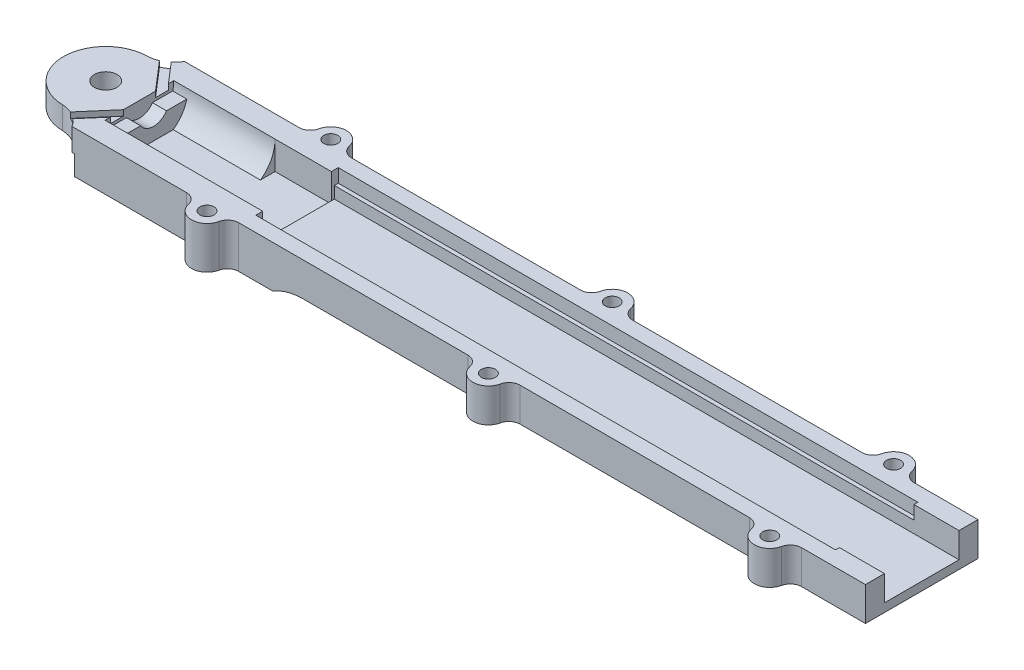
SolidWorks part; units mm, degrees
ref_plane "Front Plane" through (0, 0, 0) normal (0, 0, 1) x (1, 0, 0)
ref_plane "Top Plane" through (0, 0, 0) normal (0, 1, 0) x (1, 0, 0)
ref_plane "Right Plane" through (0, 0, 0) normal (1, 0, 0) x (0, 0, -1)
sketch "Sketch1" plane through (0, 0, 0) normal (0, 1, 0) x (1, 0, 0)
  line L0 (-32.4167, 0) -> (142.483, 0) construction
  line L3 (0, 10) -> (141, 10)
  line L4 (141, 10) -> (141, -10)
  line L5 (141, -10) -> (0, -10)
  line L8 (0, 10) -> (0, -10)
  line L9 (-4, 7.5) -> (0, 7.5)
  line L10 (-4, -7.5) -> (0, -7.5)
  circle A0 centre (-4, 0) radius 2
  arc A1 (-4, 7.5) -> (-4, -7.5) centre (-4, 0) ccw
  point P15 (141, 0)
  dimension "D1" = 4
  dimension "D2" = 4
  dimension "D3" = 145
  dimension "D5" = 7.5
  dimension "D4" = 20
extrude "Boss-Extrude1" add sketch "Sketch1" along normal mid plane 8 contours A1 L0 A0 L8 L3 | L0 A1 L5 L8 A0 region at (-5.1875, 0, -3.6496) region at (-5.1875, 0, 3.6496)
extrude "Boss-Extrude2" add sketch "Sketch1<3>" along normal mid plane 12 contours L8 L0 L4 L3 | L0 L8 L5 L4 region at (70.5, 0, -5) region at (70.5, 0, 5)
sketch "Sketch1<3>" plane through (0, 0, 0) normal (0, 1, 0) x (1, 0, 0) same geometry as "Sketch1"
sketch "Sketch3" plane through (0, 0, 0) normal (-1, 0, 0) x (0, 0, 1)
  line L0 (-3.4943, -5) -> (3.4943, -5)
  line L1 (-6.1, 0) -> (-6.1, 6)
  line L2 (-10, 6) -> (10, 6) construction
  line L3 (-6.1, 6) -> (6.1, 6)
  line L4 (6.1, 6) -> (6.1, 0)
  arc A0 (3.4943, -5) -> (6.1, 0) centre (0, 0) ccw
  arc A1 (-6.1, 0) -> (-3.4943, -5) centre (0, 0) ccw
  dimension "D1" = 12.2
  dimension "D2" = 5
extrude "Cut-Extrude1" cut sketch "Sketch3" against normal blind 18 from offset 2 offset against normal yes
sketch "Sketch4" plane through (20, 0, 0) normal (-1, 0, 0) x (0, 0, 1)
  line L0 (-6.1, 6) -> (-6.1, -5)
  line L1 (-6.1, -5) -> (6.1, -5)
  line L2 (6.1, -5) -> (6.1, 6)
  line L3 (6.1, 6) -> (-6.1, 6)
  dimension "D1" = 11
extrude "Cut-Extrude2" cut sketch "Sketch4" against normal blind 10
sketch "Sketch5" plane through (0, 0, 0) normal (-1, 0, 0) x (0, 0, 1)
  line L1 (-10, -6) -> (10, -6)
  line L2 (-10, -6) -> (-10, -8)
  line L3 (-10, -8) -> (10, -8)
  line L4 (10, -6) -> (10, -8)
  dimension "D1" = 20
  dimension "D2" = 2
extrude "Boss-Extrude3" add sketch "Sketch5" against normal blind 35
sketch "Sketch13" plane through (30, 0, 0) normal (-1, 0, 0) x (0, 0, 1)
  line L4 (-6.625, 5) -> (-6.625, -1)
  line L9 (-6.625, -1) -> (-6.625, -5)
  line L12 (-6.625, -5) -> (6.625, -5)
  line L15 (6.625, -5) -> (6.625, -1)
  line L19 (6.625, -1) -> (6.625, 5)
  line L20 (6.625, 5) -> (-6.625, 5)
  line L21 (0, 8.1097) -> (0, -11.293) construction
  point P23 (0, -5)
  point P24 (0, 5)
  dimension "D1" = 5
  dimension "D2" = 5
  dimension "D5" = 13.25
extrude "Cut-Extrude7" cut sketch "Sketch13" against normal through all
sketch "Sketch14" plane through (0, 0, 0) normal (-1, 0, 0) x (0, 0, 1)
  line L0 (10, 6) -> (10, -8) construction
  line L1 (-10, 6) -> (10, 6)
  line L2 (-10, 6) -> (-10, 4)
  line L3 (-10, 4) -> (10, 4)
  line L4 (10, 6) -> (10, 4)
  dimension "D1" = 2
extrude "Cut-Extrude8" cut sketch "Sketch14" against normal through all
fillet "Fillet2" radius 10 1 edges at (35, -6, 0)
fillet "Fillet3" radius 5 2 edges at (0, 0, 7.5) (0, 0, -7.5)
sketch "Sketch16" plane through (2, 0, 0) normal (1, 0, 0) x (0, 0, -1)
  line L0 (-6.1, 1.5) -> (-2.3049, 1.5)
  line L1 (2.3049, 1.5) -> (6.1, 1.5)
  line L2 (-5.9127, -1.5) -> (-2.3049, -1.5)
  line L3 (2.3049, -1.5) -> (5.9127, -1.5)
  line L4 (6.1, 0) -> (6.1, 4)
  line L5 (6.1, 0) -> (6.1, 4)
  line L7 (-3.4943, -5) -> (3.4943, -5)
  line L11 (-3.4943, -5) -> (3.4943, -5)
  line L16 (6.1, 4) -> (-6.1, 4)
  line L17 (6.1, 4) -> (-6.1, 4)
  line L18 (-6.1, 4) -> (-6.1, 0)
  line L19 (-6.1, 4) -> (-6.1, 0)
  arc A0 (-2.3049, -1.5) -> (2.3049, -1.5) centre (0, 0) ccw
  arc A1 (2.3049, 1.5) -> (-2.3049, 1.5) centre (0, 0) ccw
  arc A3 (-6.1, 0) -> (-3.4943, -5) centre (0, 0) ccw
  arc A4 (3.4943, -5) -> (6.1, 0) centre (0, 0) ccw
  arc A5 (-5.9127, -1.5) -> (-3.4943, -5) centre (0, 0) ccw
  arc A6 (3.4943, -5) -> (5.9127, -1.5) centre (0, 0) ccw
  arc M13 (-6.1, 0) -> (-3.4943, -5) centre (0, 0) ccw
  line M14 (-3.4943, -5) -> (3.4943, -5)
  arc M15 (3.4943, -5) -> (6.1, 0) centre (0, 0) ccw
  dimension "D1" = 0
  dimension "D2" = 5.5
  dimension "D3" = 1.5
  dimension "D4" = 1.5
sketch "Sketch20" plane through (0, 0, 0) normal (1, 0, 0) x (0, 0, -1)
  line L0 (10, 4) -> (10, -4) construction
  line L1 (10, 0) -> (-10, 0)
  line L2 (10, 0) -> (10, 4)
  line L3 (10, 4) -> (-10, 4)
  line L4 (-10, 0) -> (-10, 4)
extrude "Cut-Extrude10" cut sketch "Sketch20" against normal through all and the other way through all
extrude "Boss-Extrude5" add sketch "Sketch16" along normal blind 2.5 contours A0 L2 L3 M13 M14 M15 region at (2, -3.2591, 0)
sketch "Sketch22" plane through (0, 0, 0) normal (0, 1, 0) x (1, 0, 0)
  line L0 (-4, 0) -> (14.7321, 0) construction
  line L1 (-3.6253, 4) -> (18.01, 4) construction
  line L2 (2, 5.15) -> (2, 2.85)
  line L3 (2, 2.3049) -> (2, 5.9127) construction
  line L4 (2, 6.1) -> (2, -6.1) construction
  line L5 (2, 2.85) -> (-2.3495, 7.9057)
  line L6 (-2.3495, 7.9057) -> (-1.0642, 8.7118)
  line L7 (-1.0642, 8.7118) -> (2, 5.15)
  line L8 (2, -5.15) -> (2, -2.85)
  line L9 (-1.0642, -8.7118) -> (2, -5.15)
  line L10 (2, -2.85) -> (-2.3495, -7.9057)
  line L11 (-2.3495, -7.9057) -> (-1.0642, -8.7118)
  arc A1 (-4.1996, 7.4973) -> (0, 10) centre (-4.3327, 12.4956) ccw construction
  point P16 (2, 4)
  dimension "D2" = 1.5
  dimension "D1" = 4
  dimension "D3" = 2.3
extrude "Cut-Extrude11" cut sketch "Sketch22" against normal blind 1
sketch "Sketch25" plane through (141, 0, 0) normal (1, 0, 0) x (0, 0, -1)
  line L0 (-10, 0) -> (-10, -6) construction
  line L1 (-10, -6) -> (-10, -8)
  line L2 (-10, -8) -> (10, -8)
  line L3 (-10, -6) -> (10, -6)
  line L4 (10, -6) -> (10, -8)
  dimension "D1" = 6
  dimension "D2" = 2
  dimension "D3" = 20
sketch "Sketch26" plane through (141, 0, 0) normal (1, 0, 0) x (0, 0, -1)
  line L0 (6.625, 0) -> (6.625, -5) construction
  line L1 (-6.625, -5) -> (6.625, -5)
  line L2 (-6.625, -5) -> (-6.625, -4.5)
  line L3 (-6.625, -4.5) -> (6.625, -4.5)
  line L4 (6.625, -5) -> (6.625, -4.5)
  dimension "D1" = 0.5
extrude "Boss-Extrude6" add sketch "Sketch26" against normal up to surface (111 mm away) up to face at (30, -2.5, 6.3625)
sketch "Sketch31" plane through (0, 0, 0) normal (0, 1, 0) x (1, 0, 0)
  line L3 (-4.4, 0) -> (4.4, 0) construction
  circle A1 centre (25, 11) radius 2.75
  circle A2 centre (25, 11) radius 1.25
  circle A3 centre (75, 11) radius 2.75
  circle A4 centre (75, 11) radius 1.25
  circle A5 centre (125, 11) radius 2.75
  circle A6 centre (125, 11) radius 1.25
  circle A7 centre (125, -11) radius 1.25
  circle A8 centre (125, -11) radius 2.75
  circle A9 centre (75, -11) radius 1.25
  circle A10 centre (75, -11) radius 2.75
  circle A11 centre (25, -11) radius 1.25
  circle A12 centre (25, -11) radius 2.75
  dimension "D1" = 2.5
  dimension "D2" = 5.5
  dimension "D4" = 11
  dimension "D3" = 25
  dimension "D6" = 50
  dimension "D5" = 3
extrude "Boss-Extrude8" add sketch "Sketch31" against normal through all contours A12 | A11 | A1 | A2
extrude "Boss-Extrude9" add sketch "Sketch31<5>" against normal up to surface (6 mm away) up to face at (91, -6, 0)
sketch "Sketch31<5>" plane through (0, 0, 0) normal (0, 1, 0) x (1, 0, 0) same geometry as "Sketch31"
sketch "Sketch33" plane through (0, 0, 0) normal (0, 1, 0) x (1, 0, 0)
  circle A0 centre (25, 11) radius 1.25
  circle A1 centre (75, 11) radius 1.25
  circle A2 centre (75, -11) radius 1.25
  circle A3 centre (25, -11) radius 1.25
  circle A4 centre (125, 11) radius 1.25
  circle A5 centre (125, -11) radius 1.25
  arc A6 (24.25, -10) -> (25.75, -10) centre (25, -11) ccw construction
extrude "Cut-Extrude12" cut sketch "Sketch33" against normal through all
fillet "Fillet4" radius 2 12 edges at (122.4383, -3, -10) (72.4383, -3, -10) (22.4383, -4, -10) (127.5617, -3, -10) (77.5617, -3, -10) (27.5617, -4, -10) (127.5617, -3, 10) (77.5617, -3, 10) (122.4383, -3, 10) (72.4383, -3, 10) (22.4383, -4, 10) (27.5617, -4, 10)
sketch "Sketch34" plane through (0, 0, 0) normal (0, 1, 0) x (1, 0, 0)
  line L0 (141, 6.625) -> (30, 6.625) construction
  line L1 (30, 6.625) -> (133, 6.625)
  line L2 (30, 6.625) -> (30, 7.325)
  line L3 (30, 7.325) -> (133, 7.325)
  line L4 (133, 6.625) -> (133, 7.325)
  line L5 (30, 6.1) -> (30, -6.1) construction
  dimension "D1" = 103
  dimension "D2" = 0.7
extrude "Cut-Extrude13" cut sketch "Sketch34" against normal blind 2.4
mirror "Mirror1" about plane through (0, 0, 0) normal (0, 0, 1) of "Cut-Extrude13"
sketch "Sketch35" plane through (0, 0, 0) normal (-1, 0, 0) x (0, 0, 1)
  line L1 (-13.75, -8) -> (13.75, -8)
  line L2 (-13.75, -8) -> (-13.75, -7.5)
  line L3 (-13.75, -7.5) -> (13.75, -7.5)
  line L4 (13.75, -8) -> (13.75, -7.5)
  line L5 (-10, -8) -> (10, -8) construction
  line L6 (13.75, -8) -> (13.75, 0) construction
  dimension "D1" = 0.5
extrude "Cut-Extrude14" cut sketch "Sketch35" against normal up to next
sketch "Sketch36" plane through (0, 0, 10) normal (0, 0, 1) x (1, 0, 0)
  line L0 (-4.1996, -4) -> (0, -4) construction
  line L1 (0, -7.5) -> (0.5, -7.5)
  line L2 (0, -7.5) -> (0, -4)
  line L3 (0, -4) -> (0.5, -4)
  line L4 (0.5, -7.5) -> (0.5, -4)
  dimension "D1" = 0.5
extrude "Cut-Extrude15" cut sketch "Sketch36" against normal up to next
